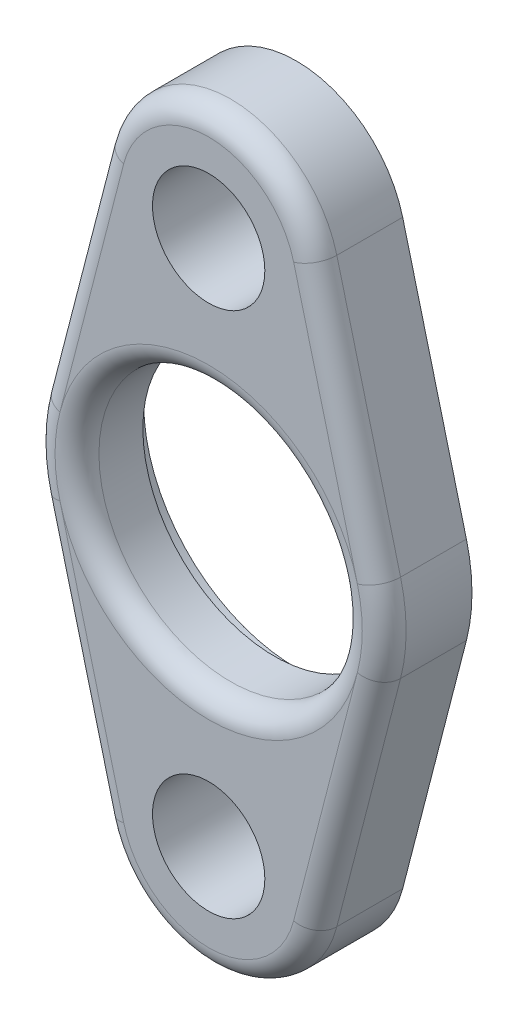
SolidWorks part; units mm, degrees
ref_plane "Front Plane" through (0, 0, 0) normal (0, 0, 1) x (1, 0, 0)
ref_plane "Top Plane" through (0, 0, 0) normal (0, 1, 0) x (1, 0, 0)
ref_plane "Right Plane" through (0, 0, 0) normal (1, 0, 0) x (0, 0, -1)
sketch "Sketch1" plane through (0, 0, 0) normal (0, 0, 1) x (1, 0, 0)
  line L0 (0, -9.525) -> (0, 0) construction
  line L1 (0, 0) -> (0, 9.525) construction
  line L2 (3.8427, -10.5172) -> (6.1484, -1.5875)
  line L3 (6.1484, 1.5875) -> (3.8427, 10.5172)
  line L4 (-6.1484, -1.5875) -> (-3.8427, -10.5172)
  line L5 (-3.8427, 10.5172) -> (-6.1484, 1.5875)
  circle A0 centre (0, 9.525) radius 2.032
  circle A1 centre (0, -9.525) radius 2.032
  circle A2 centre (0, 0) radius 4.7625
  arc A3 (-3.8427, -10.5172) -> (3.8427, -10.5172) centre (0, -9.525) ccw
  arc A4 (6.1484, -1.5875) -> (6.1484, 1.5875) centre (0, 0) ccw
  arc A5 (3.8427, 10.5172) -> (-3.8427, 10.5172) centre (0, 9.525) ccw
  arc A7 (-6.1484, 1.5875) -> (-6.1484, -1.5875) centre (0, 0) ccw
  dimension "D1" = 4.064
  dimension "D3" = 9.525
  dimension "D4" = 6.35
  dimension "D5" = 3.9688
  dimension "D2" = 9.525
extrude "Boss-Extrude1" add sketch "Sketch1" along normal blind 3.175
sketch "Sketch2" plane through (0, 0, 0) normal (0, 0, -1) x (-1, 0, 0)
  circle A0 centre (0, 0) radius 5.5245
  dimension "D1" = 11.049
extrude "Cut-Extrude3" cut sketch "Sketch2" against normal blind 0.7937
fillet "Fillet1" radius 0.7937 9 edges at (6.35, 0, 3.175) (4.9955, -6.0523, 3.175) (0, -13.4938, 3.175) (-4.9955, -6.0523, 3.175) (-6.35, 0, 3.175) (-4.9955, 6.0523, 3.175) (0, 13.4938, 3.175) (4.7625, 0, 3.175) (4.9955, 6.0523, 3.175)
